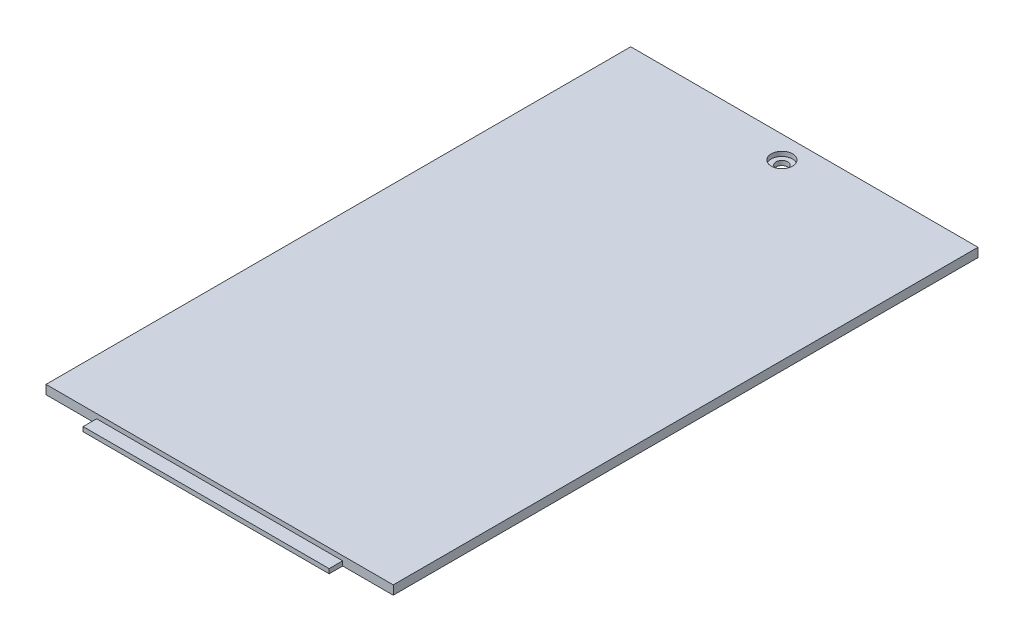
SolidWorks part; units mm, degrees
material "PLA"
ref_plane "Спереди" through (0, 0, 0) normal (0, 0, 1) x (1, 0, 0)
ref_plane "Сверху" through (0, 0, 0) normal (0, 1, 0) x (1, 0, 0)
ref_plane "Справа" through (0, 0, 0) normal (1, 0, 0) x (0, 0, -1)
sketch "Эскиз1" plane through (0, 0, 0) normal (0, 1, 0) x (1, 0, 0)
  line L1 (38.6, 65) -> (-38.6, 65)
  line L2 (38.6, 65) -> (38.6, -65)
  line L3 (38.6, -65) -> (-38.6, -65)
  line L4 (-38.6, 65) -> (-38.6, -65)
  line L5 (38.6, 65) -> (-38.6, -65) construction
  line L6 (38.6, -65) -> (-38.6, 65) construction
  point P0 (0, 0)
  dimension "D1" = 77.2
  dimension "D2" = 130
extrude "Бобышка-Вытянуть1" add sketch "Эскиз1" along normal blind 2
sketch "Эскиз3" plane through (0, 2, 0) normal (0, 1, 0) x (1, 0, 0)
  line L0 (0, 0) -> (0, 50000) construction
  line L1 (38.6, 65) -> (-38.6, 65) construction
  circle A0 centre (0, 60) radius 1.3
  dimension "D1" = 2.6
  dimension "D2" = 5
extrude "Вырез-Вытянуть1" cut sketch "Эскиз3" against normal through all
sketch "Эскиз5" plane through (0, 2, 0) normal (0, 1, 0) x (1, 0, 0)
  circle A0 centre (0, 60) radius 2.375
  dimension "D1" = 4.75
extrude "Вырез-Вытянуть2" cut sketch "Эскиз5" against normal blind 1
sketch "Эскиз6" plane through (0, 0, 65) normal (0, 0, 1) x (1, 0, 0)
  line L0 (0, 0) -> (0, 50000) construction
  line L1 (-38.6, 0) -> (38.6, 0) construction
  line L3 (27.35, 1) -> (-27.35, 1)
  line L4 (27.35, 1) -> (27.35, 0)
  line L5 (27.35, 0) -> (-27.35, 0)
  line L6 (-27.35, 1) -> (-27.35, 0)
  line L7 (27.35, 1) -> (-27.35, 0) construction
  line L8 (27.35, 0) -> (-27.35, 1) construction
  point P4 (0, 0)
  point P5 (0, 0.5)
  dimension "D1" = 54.7
  dimension "D2" = 1
extrude "Бобышка-Вытянуть2" add sketch "Эскиз6" along normal blind 3
